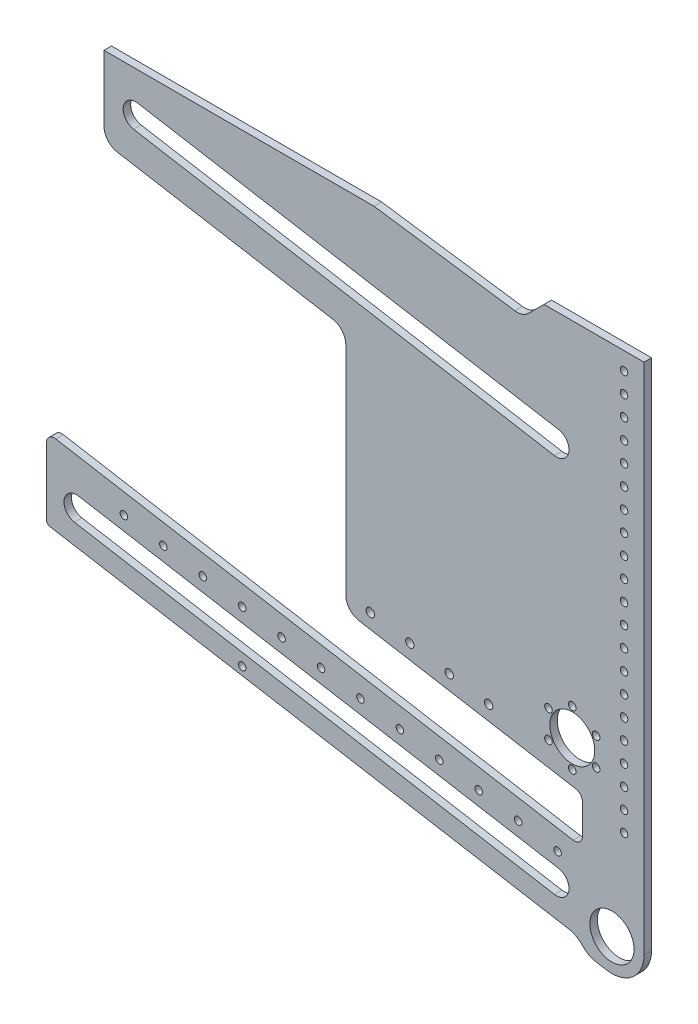
SolidWorks part; units mm, degrees
material "Polypropylene"
ref_plane "Front Plane" through (0, 0, 0) normal (0, 0, 1) x (1, 0, 0)
ref_plane "Top Plane" through (0, 0, 0) normal (0, 1, 0) x (1, 0, 0)
ref_plane "Right Plane" through (0, 0, 0) normal (1, 0, 0) x (0, 0, -1)
sketch "Sketch1" plane through (0, 0, 0) normal (0, 0, 1) x (1, 0, 0)
  line L0 (19.05, 0) -> (19.05, -76.2) construction
  line L1 (0, 19.05) -> (-57.15, 19.05) construction
  line L2 (19.05, -155.575) -> (168.9894, -155.575) construction
  line L3 (0, -95.25) -> (-57.15, -95.25) construction
  line L4 (-57.15, -95.25) -> (-57.15, 19.05) construction
  line L5 (168.9894, 7.239) -> (168.9894, -18.161) construction
  line L6 (168.9894, -18.161) -> (168.9894, -155.575) construction
  line L7 (168.9894, 7.239) -> (143.6189, 6.0141) construction
  line L8 (143.6189, 6.0141) -> (19.05, 0) construction
  line L9 (165.5424, -12.8509) -> (158.8645, -11.7052)
  line L10 (189.3729, 7.239) -> (189.3729, 131.5601)
  line L12 (197.5644, 110.4886) -> (197.5644, -33.1911) construction
  line L16 (-190.0576, 99.3321) -> (-190.0576, 56.7465)
  line L17 (133.7924, 19.9786) -> (-171.0076, 72.2757) construction
  line L18 (132.4501, 12.1554) -> (-172.3499, 64.4526)
  line L19 (135.1346, 27.8017) -> (-169.6654, 80.0989)
  line L20 (-184.1635, 104.3011) -> (139.1268, 48.8314)
  line L23 (-187.9472, 54.2431) -> (141.5847, -2.2975)
  line L24 (176.6729, 131.5601) -> (176.6729, 118.8601) construction
  line L25 (176.6729, 118.8601) -> (189.3729, 118.8601) construction
  line L31 (139.1268, 48.8314) -> (144.2855, 47.9463)
  line L32 (150.2246, 52.9531) -> (150.2246, 72.0031)
  line L38 (146.0036, 77.01) -> (8.4683, 100.6081)
  line L40 (189.3729, 131.5601) -> (189.3729, 333.3075)
  line L42 (-153.5271, 291.5636) -> (-153.5271, 333.3075)
  line L43 (-153.5271, 333.3075) -> (189.3729, 333.3075)
  line L51 (34.3472, 54.0166) -> (40.7189, 104.4154) construction
  line L53 (133.7924, 261.2786) -> (-133.4156, 307.1258) construction
  line L54 (132.4501, 253.4554) -> (-134.7579, 299.3026)
  line L55 (135.1346, 269.1017) -> (-132.0734, 314.9489)
  line L56 (-145.0853, 281.55) -> (-8.4155, 258.1003)
  line L57 (0.0264, 248.0867) -> (0.0264, 110.6218)
  arc A0 (19.05, 0) -> (0, 19.05) centre (0, 0) ccw construction
  arc A1 (19.05, -76.2) -> (0, -95.25) centre (0, -76.2) cw construction
  circle A2 centre (168.9894, 7.239) radius 14.0335
  arc A3 (168.9894, -18.161) -> (143.6189, 6.0141) centre (168.9894, 7.239) ccw construction
  arc A4 (165.5424, -12.8509) -> (189.3729, 7.239) centre (168.9894, 7.239) ccw
  arc A5 (132.4501, 12.1554) -> (135.1346, 27.8017) centre (133.7924, 19.9786) ccw
  arc A6 (-169.6654, 80.0989) -> (-172.3499, 64.4526) centre (-171.0076, 72.2757) ccw
  circle A8 centre (176.6729, 118.8601) radius 2.3813
  circle A9 centre (176.6729, 106.1601) radius 2.3813
  circle A10 centre (176.6729, 93.4601) radius 2.3813
  circle A11 centre (176.6729, 80.7601) radius 2.3813
  circle A12 centre (176.6729, 68.0601) radius 2.3813
  circle A15 centre (109.4497, 41.1306) radius 2.3813
  circle A16 centre (84.4155, 45.4259) radius 2.3812
  circle A17 centre (59.3813, 49.7212) radius 2.3813
  circle A18 centre (34.3472, 54.0166) radius 2.3813
  circle A19 centre (9.313, 58.3119) radius 2.3813
  circle A20 centre (-15.7212, 62.6072) radius 2.3812
  circle A21 centre (-40.7554, 66.9026) radius 2.3813
  circle A22 centre (-65.7896, 71.1979) radius 2.3813
  circle A23 centre (-90.8237, 75.4932) radius 2.3812
  circle A24 centre (-115.8579, 79.7886) radius 2.3813
  circle A25 centre (-140.8921, 84.0839) radius 2.3812
  circle A28 centre (134.4839, 36.8353) radius 2.3813
  arc A31 (-187.9472, 54.2431) -> (-190.0576, 56.7465) centre (-187.5176, 56.7465) cw
  arc A34 (158.8645, -11.7052) -> (150.2246, -7.0013) centre (161.4417, 3.3154) cw
  circle A39 centre (143.8098, 103.921) radius 21.9964 construction
  circle A40 centre (143.8098, 103.921) radius 14.2875
  circle A41 centre (143.8098, 103.921) radius 17.4625 construction
  circle A42 centre (143.8098, 121.3835) radius 2.413
  circle A43 centre (158.9328, 112.6523) radius 2.413
  circle A44 centre (158.9328, 95.1898) radius 2.413
  circle A45 centre (143.8098, 86.4585) radius 2.413
  circle A46 centre (128.6869, 95.1898) radius 2.413
  circle A47 centre (128.6869, 112.6523) radius 2.413
  arc A48 (141.5847, -2.2975) -> (150.2246, -7.0013) centre (139.0075, -17.318) cw
  arc A49 (144.2855, 47.9463) -> (150.2246, 52.9531) centre (145.1446, 52.9531) ccw
  arc A53 (-190.0576, 99.3321) -> (-184.1635, 104.3011) centre (-185.016, 99.3321) cw
  arc A55 (150.2246, 72.0031) -> (146.0036, 77.01) centre (145.1446, 72.0031) ccw
  circle A57 centre (176.6729, 131.5601) radius 2.3813
  circle A58 centre (176.6729, 144.2601) radius 2.3813
  circle A59 centre (176.6729, 156.9601) radius 2.3813
  circle A60 centre (176.6729, 169.6601) radius 2.3813
  circle A61 centre (176.6729, 182.3601) radius 2.3813
  circle A62 centre (176.6729, 195.0601) radius 2.3813
  circle A63 centre (176.6729, 207.7601) radius 2.3813
  circle A64 centre (176.6729, 220.4601) radius 2.3813
  circle A65 centre (176.6729, 233.1601) radius 2.3813
  circle A66 centre (176.6729, 245.8601) radius 2.3813
  circle A67 centre (176.6729, 258.5601) radius 2.3813
  circle A68 centre (176.6729, 271.2601) radius 2.3813
  circle A69 centre (176.6729, 283.9601) radius 2.3813
  circle A70 centre (176.6729, 296.6601) radius 2.3813
  circle A71 centre (176.6729, 309.3601) radius 2.3813
  circle A72 centre (176.6729, 322.0601) radius 2.3813
  circle A86 centre (15.6017, 108.7237) radius 2.667
  circle A88 centre (40.636, 104.4296) radius 2.667
  circle A90 centre (65.6704, 100.1355) radius 2.667
  circle A92 centre (90.7048, 95.8414) radius 2.667
  arc A95 (132.4501, 253.4554) -> (135.1346, 269.1017) centre (133.7924, 261.2786) ccw
  arc A96 (-132.0734, 314.9489) -> (-134.7579, 299.3026) centre (-133.4156, 307.1258) ccw
  circle A97 centre (-65.7896, 38.501) radius 2.3876
  arc A98 (-153.5271, 291.5636) -> (-145.0853, 281.55) centre (-143.3671, 291.5636) ccw
  arc A99 (-8.4155, 258.1003) -> (0.0264, 248.0867) centre (-10.1336, 248.0867) cw
  arc A100 (8.4683, 100.6081) -> (0.0264, 110.6218) centre (10.1864, 110.6218) cw
  point P24 (-18.6076, 46.1272)
  point P51 (-190.0576, 48.1625)
  point P92 (143.8191, 3.8303)
  point P95 (150.6057, -10.2881)
  point P107 (-190.0576, 105.3125)
  point P118 (143.8098, 103.921)
  point P162 (0.1884, 284.2022)
  dimension "D1" = 19.05
  dimension "D4" = 19.05
  dimension "D6" = 28.067
  dimension "D7" = 50.8
  dimension "D15" = 7.9375
  dimension "D24" = 4.7625
  dimension "D26" = 2.54
  dimension "D27" = 15.24
  dimension "D31" = 43.9928
  dimension "D32" = 34.925
  dimension "D34" = 4.826
  dimension "D19" = 28.575
  dimension "D25" = 5.08
  dimension "D30" = 5.08
  dimension "D33" = 4.7752
  dimension "D45" = 10.16
  dimension "D2" = 155.575
  dimension "D3" = 76.2
  dimension "D5" = 114.3
  dimension "D8" = 137.414
  dimension "D9" = 124.714
  dimension "D10" = 6.35
  dimension "D11" = 12.5
  dimension "D12" = 355.6
  dimension "D14" = 57.15
  dimension "D13" = 28.575
  dimension "D16" = 19.05
  dimension "D18" = 304.8
  dimension "D22" = 12.7
  dimension "D28" = 12.7
  dimension "D37" = 342.9
  dimension "D38" = 19.05
  dimension "D39" = 12.7
  dimension "D17" = 55.5805
  dimension "D29" = 12.7
  dimension "D40" = 17.2798
  dimension "D41" = 9.4076
  dimension "D42" = 39.1483
  dimension "D44" = 241.3
  dimension "D21" = 50.8
  dimension "D43" = 267.208
  dimension "D23" = 5
  dimension "D20" = 2
  dimension "D36" = 17
  dimension "D35" = 6
extrude "Boss-Extrude1" add sketch "Sketch1" along normal blind 4.7625
sketch "Sketch2" plane through (0, 0, 4.7625) normal (0, 0, 1) x (1, 0, 0)
  line L0 (-188.8187, 48.0143) -> (-189.0355, 50.6158)
  line L1 (-189.2877, 50.8909) -> (-190.3122, 51.0667)
  line L2 (-190.6416, 50.8914) -> (-191.7133, 48.5109)
  line L3 (-191.7725, 48.4567) -> (-191.7682, 48.4817) construction
  line L4 (-189.7999, 50.9788) -> (-190.2767, 48.2) construction
  line L5 (-188.7766, 49.257) -> (-191.3387, 49.6966) construction
  line L6 (158.8645, -11.7052) -> (165.5424, -12.8509) construction
  line L7 (-191.1909, 49.6712) -> (-191.4434, 48.2) construction
  line L8 (-188.9244, 49.2823) -> (-189.1101, 48.2) construction
  line L11 (-188.7809, 47.9434) -> (-191.7725, 48.4567)
  line L13 (-188.7766, 47.9684) -> (-188.306, 47.8877)
  line L14 (-188.306, 47.8877) -> (-188.3103, 47.8626)
  line L15 (-188.3103, 47.8626) -> (-188.7809, 47.9434)
  line L16 (-188.7809, 47.9434) -> (-188.7766, 47.9684) construction
  line L17 (-192.2389, 48.5625) -> (-192.2431, 48.5374)
  line L18 (-192.2431, 48.5374) -> (-191.7725, 48.4567)
  line L19 (-191.7682, 48.4817) -> (-192.2389, 48.5625)
  line L21 (-190.0576, 99.3321) -> (-190.0576, 56.7465) construction
  arc A0 (-190.3122, 51.0667) -> (-190.6416, 50.8914) centre (-190.3637, 50.7663) ccw
  arc A1 (-189.0355, 50.6158) -> (-189.2877, 50.8909) centre (-189.3392, 50.5905) ccw
  arc A2 (-191.7682, 48.4817) -> (-191.7133, 48.5109) centre (-191.7596, 48.5318) ccw
  arc A3 (-188.8187, 48.0143) -> (-188.7766, 47.9684) centre (-188.768, 48.0185) ccw
  point P6 (-190.0576, 49.4768)
  dimension "D1" = 0.0254
  dimension "Root_fillet" = 0.3048
  dimension "Break_rad" = 0.0508
  dimension "Gap_width" = 2.2997
  dimension "Dedendum" = 1.524
  dimension "Addendum_plus" = 1.2954
  dimension "Pressure_angle" = 14.5
  dimension "D2" = 0.4775
sketch "Sketch3" plane through (0, 0, 4.7625) normal (0, 0, 1) x (1, 0, 0)
  line L6 (189.3729, 333.3075) -> (125.8729, 333.3075) construction
  line L7 (189.3729, 333.3075) -> (-153.5271, 333.3075) construction
  line L8 (125.8729, 333.3075) -> (115.9933, 323.428)
  line L9 (107.3751, 320.5539) -> (17.9229, 333.3075)
  line L10 (125.8729, 333.3075) -> (17.9229, 333.3075)
  arc A0 (115.9933, 323.428) -> (107.3751, 320.5539) centre (108.8091, 330.6122) cw
  dimension "D1" = 10.16
extrude "Cut-Extrude1" cut sketch "Sketch3" against normal through all
equation "\"D18@Sketch1\"=13.25-1.25"
equation "\"D12@Sketch1\"=15.25-1.25"
